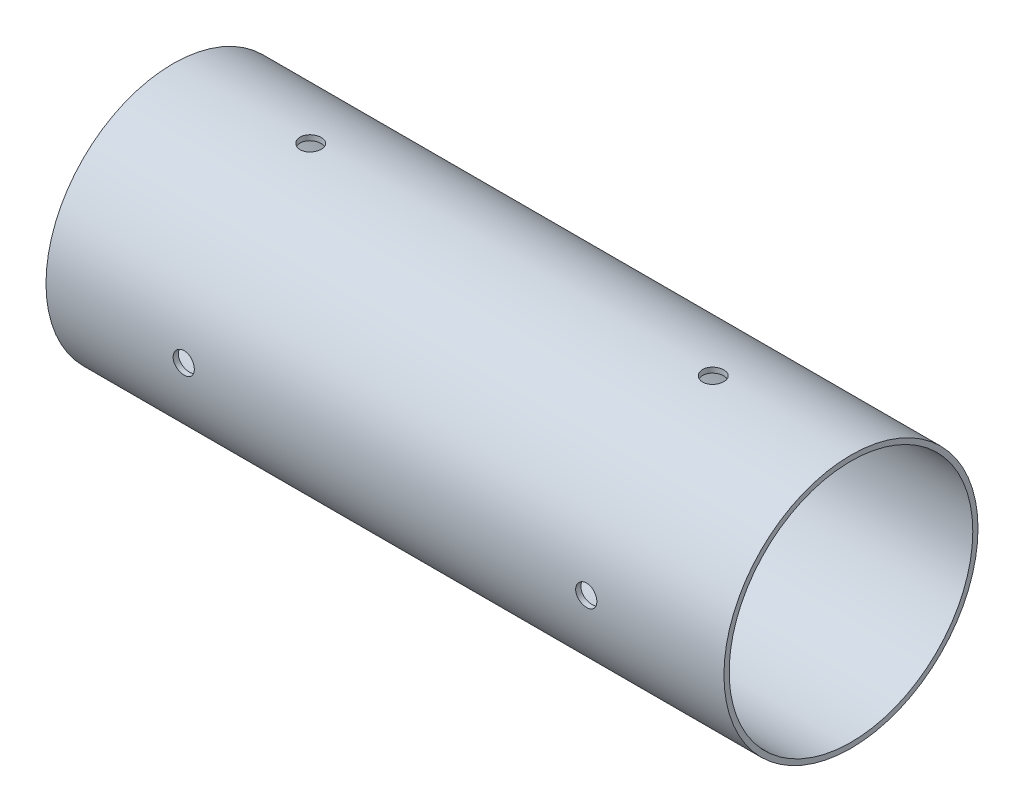
SolidWorks part; units mm, degrees
ref_plane "Front Plane" through (0, 0, 0) normal (1, 0, 0) x (0, 1, 0)
ref_plane "Top Plane" through (0, 0, 0) normal (0, 0, 1) x (0, 1, 0)
ref_plane "Right Plane" through (0, 0, 0) normal (0, 1, 0) x (-1, 0, 0)
sketch "Sketch1" plane through (0, 0, 0) normal (1, 0, 0) x (0, 1, 0)
  circle A0 centre (0, 0) radius 36.5125
  circle A1 centre (0, 0) radius 38.0746
  dimension "D1" = 73.025
  dimension "D2" = 76.1492
extrude "Boss-Extrude1" add sketch "Sketch1" along normal blind 203.2
sketch "Sketch3" plane through (0, 0, 0) normal (0, 1, 0) x (-1, 0, 0)
  line L0 (-203.2, 38.0746) -> (-203.2, -38.0746) construction
  circle A0 centre (-161.925, 0) radius 3.175
  dimension "D2" = 6.35
  dimension "D1" = 41.275
extrude "Cut-Extrude1" cut sketch "Sketch3" along normal through all
pattern_circular "CirPattern1" count 4 over 360 about axis through (203.2, 0, 0) along (-1, 0, 0) of "Cut-Extrude1"
sketch "Sketch4" plane through (0, 0, 0) normal (0, 1, 0) x (-1, 0, 0)
  circle A0 centre (-41.275, 0) radius 3.175
  dimension "D1" = 6.35
  dimension "D2" = 41.275
extrude "Cut-Extrude2" cut sketch "Sketch4" along normal through all
pattern_circular "CirPattern2" count 4 over 360 about axis through (203.2, 0, 0) along (-1, 0, 0) of "Cut-Extrude2" reverse direction yes
